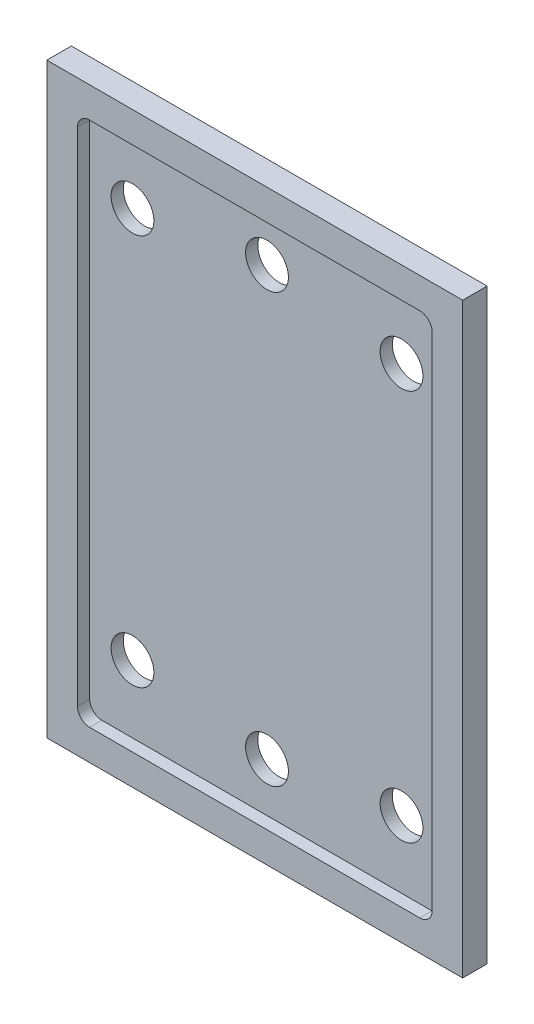
SolidWorks part; units mm, degrees
ref_plane "Front Plane" through (0, 0, 0) normal (0, 0, 1) x (1, 0, 0)
ref_plane "Top Plane" through (0, 0, 0) normal (0, 1, 0) x (1, 0, 0)
ref_plane "Right Plane" through (0, 0, 0) normal (1, 0, 0) x (0, 0, -1)
sketch "Sketch1" plane through (0, 0, 0) normal (0, 0, 1) x (1, 0, 0)
  line L1 (107.95, -152.4) -> (-107.95, -152.4)
  line L2 (107.95, -152.4) -> (107.95, 152.4)
  line L3 (107.95, 152.4) -> (-107.95, 152.4)
  line L4 (-107.95, -152.4) -> (-107.95, 152.4)
  line L5 (107.95, -152.4) -> (-107.95, 152.4) construction
  line L6 (107.95, 152.4) -> (-107.95, -152.4) construction
  point P0 (0, 0)
  dimension "D1" = 215.9
  dimension "D2" = 304.8
extrude "Boss-Extrude1" add sketch "Sketch1" along normal blind 12.7
sketch "Sketch2" plane through (0, 0, 12.7) normal (0, 0, 1) x (1, 0, 0)
  line L0 (-107.95, 152.4) -> (-107.95, -152.4) construction
  line L1 (85.725, -136.525) -> (-85.725, -136.525)
  line L2 (92.075, -130.175) -> (92.075, 130.175)
  line L3 (85.725, 136.525) -> (-85.725, 136.525)
  line L4 (-92.075, -130.175) -> (-92.075, 130.175)
  line L5 (92.075, -136.525) -> (-92.075, 136.525) construction
  line L6 (92.075, 136.525) -> (-92.075, -136.525) construction
  line L7 (107.95, 152.4) -> (-107.95, 152.4) construction
  arc A0 (-85.725, -136.525) -> (-92.075, -130.175) centre (-85.725, -130.175) cw
  arc A1 (85.725, -136.525) -> (92.075, -130.175) centre (85.725, -130.175) ccw
  arc A2 (92.075, 130.175) -> (85.725, 136.525) centre (85.725, 130.175) ccw
  arc A3 (-85.725, 136.525) -> (-92.075, 130.175) centre (-85.725, 130.175) ccw
  point P0 (0, 0)
  dimension "D3" = 6.35
  dimension "D1" = 15.875
  dimension "D2" = 15.875
extrude "Cut-Extrude1" cut sketch "Sketch2" against normal blind 6.35
sketch "Sketch4" plane through (0, 0, 6.35) normal (0, 0, 1) x (1, 0, 0)
  line L0 (107.95, 152.4) -> (-107.95, 152.4) construction
  line L4 (-107.95, 152.4) -> (-107.95, -152.4) construction
  line L5 (107.95, -152.4) -> (107.95, 152.4) construction
  line L6 (-107.95, -152.4) -> (107.95, -152.4) construction
  line L7 (85.725, 136.525) -> (-85.725, 136.525) construction
  line L8 (-85.725, -136.525) -> (85.725, -136.525) construction
  circle A0 centre (-69.85, 101.6) radius 11.1125
  circle A1 centre (69.85, 101.6) radius 11.1125
  circle A2 centre (-69.85, -101.6) radius 11.1125
  circle A3 centre (69.85, -101.6) radius 11.1125
  circle A4 centre (0, 111.125) radius 11.1125
  circle A5 centre (0, -111.125) radius 11.1125
  point P24 (0, 0)
  point P26 (0, 0)
  dimension "D1" = 22.225
  dimension "D2" = 22.225
  dimension "D3" = 22.225
  dimension "D4" = 22.225
  dimension "D13" = 22.225
  dimension "D14" = 22.225
  dimension "D15" = 25.4
  dimension "D5" = 50.8
  dimension "D6" = 38.1
  dimension "D7" = 38.1
  dimension "D8" = 0
  dimension "D9" = 50.8
  dimension "D10" = 38.1
  dimension "D11" = 38.1
  dimension "D12" = 50.8
  dimension "D16" = 25.4
extrude "Cut-Extrude2" cut sketch "Sketch4" against normal through all
